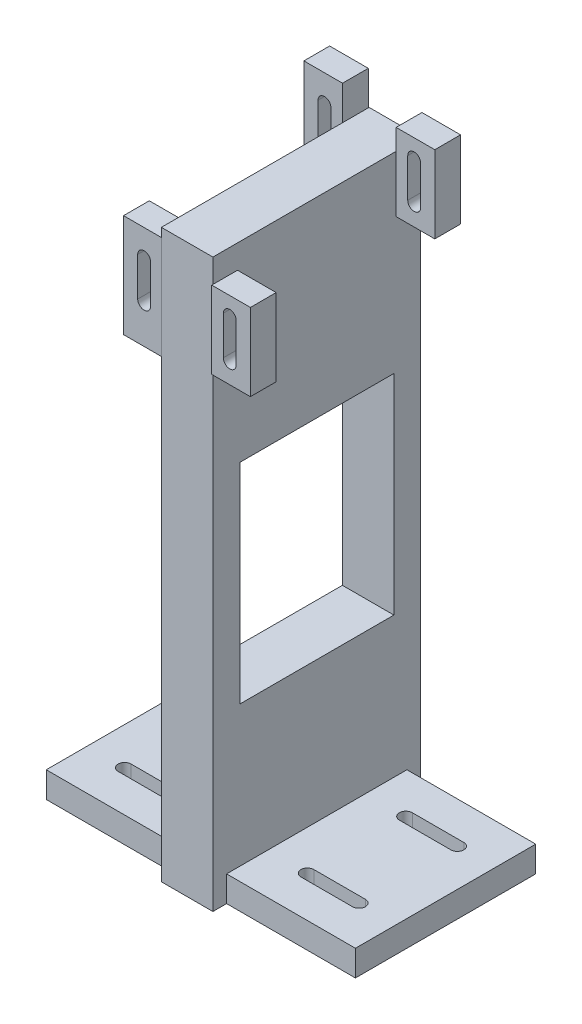
SolidWorks part; units mm, degrees
ref_plane "Płaszczyzna przednia" through (0, 0, 0) normal (0, 0, 1) x (1, 0, 0)
ref_plane "Płaszczyzna górna" through (0, 0, 0) normal (0, 1, 0) x (1, 0, 0)
ref_plane "Płaszczyzna prawa" through (0, 0, 0) normal (1, 0, 0) x (0, 0, -1)
sketch "Sketch1" plane through (0, 0, 0) normal (0, 1, 0) x (1, 0, 0)
  line L0 (-60, 0) -> (60, 0) construction
  line L1 (-60, 35) -> (60, 35)
  line L2 (-60, 35) -> (-60, -35)
  line L3 (-60, -35) -> (60, -35)
  line L4 (60, 35) -> (60, -35)
  line L5 (0, 35) -> (0, -35) construction
  line L6 (-10, 40.3147) -> (-10, -40.3147)
  line L7 (10, 40.3147) -> (10, -40.3147)
  line L8 (-45.4696, 19.1036) -> (-25.4696, 19.1036) construction
  line L9 (-45.4696, 21.6036) -> (-25.4696, 21.6036)
  line L10 (-45.4696, 16.6036) -> (-25.4696, 16.6036)
  line L11 (45.4696, 19.1036) -> (25.4696, 19.1036) construction
  line L13 (45.4696, 21.6036) -> (25.4696, 21.6036)
  line L14 (45.4696, 16.6036) -> (25.4696, 16.6036)
  line L15 (45.4696, -19.1036) -> (25.4696, -19.1036) construction
  line L16 (45.4696, -21.6036) -> (25.4696, -21.6036)
  line L17 (45.4696, -16.6036) -> (25.4696, -16.6036)
  line L18 (-45.4696, -19.1036) -> (-25.4696, -19.1036) construction
  line L19 (-45.4696, -21.6036) -> (-25.4696, -21.6036)
  line L20 (-45.4696, -16.6036) -> (-25.4696, -16.6036)
  line L21 (-10, 40.3147) -> (10, 40.3147)
  line L22 (10, -40.3147) -> (-10, -40.3147)
  arc A8 (-45.4696, 21.6036) -> (-45.4696, 16.6036) centre (-45.4696, 19.1036) ccw
  arc A9 (-25.4696, 16.6036) -> (-25.4696, 21.6036) centre (-25.4696, 19.1036) ccw
  arc A10 (45.4696, 21.6036) -> (45.4696, 16.6036) centre (45.4696, 19.1036) cw
  arc A11 (25.4696, 16.6036) -> (25.4696, 21.6036) centre (25.4696, 19.1036) cw
  arc A12 (45.4696, -21.6036) -> (45.4696, -16.6036) centre (45.4696, -19.1036) ccw
  arc A13 (25.4696, -16.6036) -> (25.4696, -21.6036) centre (25.4696, -19.1036) ccw
  arc A14 (-45.4696, -21.6036) -> (-45.4696, -16.6036) centre (-45.4696, -19.1036) cw
  arc A15 (-25.4696, -16.6036) -> (-25.4696, -21.6036) centre (-25.4696, -19.1036) cw
  point P17 (-35.4696, 19.1036)
  point P30 (35.4696, 19.1036)
  point P41 (35.4696, -19.1036)
  point P48 (-35.4696, -19.1036)
  dimension "D4" = 20
  dimension "D1" = 120
  dimension "D2" = 70
  dimension "D3" = 20
  dimension "D6" = 5
extrude "Boss-Extrude1" add sketch "Sketch1" along normal blind 10 contours A15 L20 A14 L19 | L10 A9 L9 A8 | A11 L14 A10 L13 | L17 A13 L16 A12 | L3 L4 L1 L2 region at (-35.4696, 0, -19.1036) region at (35.4696, 0, -19.1036) region at (35.4696, 0, 19.1036) region at (-35.4696, 0, 19.1036)
extrude "Boss-Extrude2" add sketch "Sketch1<3>" along normal blind 220 contours L7 L1 L6 L3 | L21 L6 L1 L7 | L22 L7 L3 L6 region at (0, 0, -37.6574) region at (0, 0, 0) region at (0, 0, 37.6574)
sketch "Sketch1<3>" plane through (0, 0, 0) normal (0, 1, 0) x (1, 0, 0) same geometry as "Sketch1"
sketch "Sketch2" plane through (10, 0, 0) normal (1, 0, 0) x (0, 0, -1)
  line L5 (-30, 216.2685) -> (-40, 216.2685)
  line L6 (-30, 216.2685) -> (-30, 176.2685)
  line L7 (-30, 176.2685) -> (-40, 176.2685)
  line L8 (-40, 216.2685) -> (-40, 176.2685)
  line L10 (30, 233.2933) -> (40, 233.2933)
  line L11 (30, 233.2933) -> (30, 158.5233)
  line L12 (30, 158.5233) -> (40, 158.5233)
  line L13 (40, 233.2933) -> (40, 158.5233)
  line L14 (0, 220) -> (0, 77.9938) construction
  line L15 (40.3147, 220) -> (-40.3147, 220) construction
  dimension "D1" = 60
  dimension "D2" = 10
  dimension "D3" = 40
extrude "Boss-Extrude3" add sketch "Sketch2" against normal blind 15 from surface starting at face at (-10, 57.5, 0)
sketch "Sketch3" plane through (10, 0, 0) normal (1, 0, 0) x (0, 0, -1)
  line L1 (-29.7814, 145.7552) -> (29.9449, 145.7552)
  line L2 (-29.7814, 145.7552) -> (-29.7814, 64.5274)
  line L3 (-29.7814, 64.5274) -> (29.9449, 64.5274)
  line L4 (29.9449, 145.7552) -> (29.9449, 64.5274)
extrude "Cut-Extrude1" cut sketch "Sketch3" against normal blind 60
sketch "Sketch4" plane through (0, 0, 40) normal (0, 0, 1) x (1, 0, 0)
  line L0 (-17, 205.9837) -> (-17, 190.9837) construction
  line L1 (-14.5, 205.9837) -> (-14.5, 190.9837)
  line L2 (-19.5, 205.9837) -> (-19.5, 190.9837)
  line L3 (-10, 220) -> (-10, 0) construction
  arc A0 (-14.5, 205.9837) -> (-19.5, 205.9837) centre (-17, 205.9837) ccw
  arc A1 (-19.5, 190.9837) -> (-14.5, 190.9837) centre (-17, 190.9837) ccw
  point P2 (-17, 198.4837)
  point P7 (-19.0815, 198.3469)
  point P10 (-17, 205.9837)
  point P11 (0, 0)
  dimension "D1" = 5
  dimension "D2" = 15
  dimension "D3" = 7
extrude "Cut-Extrude2" cut sketch "Sketch4" against normal up to next
sketch "Sketch5" plane through (0, 0, -40) normal (0, 0, -1) x (-1, 0, 0)
  line L0 (17, 222.8197) -> (17, 207.8197) construction
  line L1 (19.5, 222.8197) -> (19.5, 207.8197)
  line L2 (14.5, 222.8197) -> (14.5, 207.8197)
  line L3 (10, 220) -> (10, 233.2933) construction
  line L4 (17, 183.2065) -> (17, 168.2065) construction
  line L5 (19.5, 183.2065) -> (19.5, 168.2065)
  line L6 (14.5, 183.2065) -> (14.5, 168.2065)
  arc A0 (19.5, 222.8197) -> (14.5, 222.8197) centre (17, 222.8197) ccw
  arc A1 (14.5, 207.8197) -> (19.5, 207.8197) centre (17, 207.8197) ccw
  arc A2 (19.5, 183.2065) -> (14.5, 183.2065) centre (17, 183.2065) ccw
  arc A3 (14.5, 168.2065) -> (19.5, 168.2065) centre (17, 168.2065) ccw
  point P2 (17, 215.3197)
  point P11 (17, 175.7065)
  point P16 (17, 169.0011)
  point P17 (17, 174.696)
  point P18 (17, 176.3471)
  point P19 (17, 175.7065)
  point P20 (17, 215.3197)
  dimension "D1" = 15
  dimension "D2" = 5
  dimension "D3" = 7
extrude "Cut-Extrude3" cut sketch "Sketch5" against normal up to next
ref_plane "Plane1" through (0, 0, 0) normal (0, 0, 1) x (1, 0, 0)
sketch "Sketch6" plane through (10, 0, 0) normal (1, 0, 0) x (0, 0, -1)
  line L1 (-30.7639, 210.7964) -> (-40.7639, 210.7964)
  line L2 (-30.7639, 210.7964) -> (-30.7639, 180.7964)
  line L3 (-30.7639, 180.7964) -> (-40.7639, 180.7964)
  line L4 (-40.7639, 210.7964) -> (-40.7639, 180.7964)
  line L5 (30.8125, 228.0299) -> (40.8125, 228.0299)
  line L6 (30.8125, 228.0299) -> (30.8125, 198.0299)
  line L7 (30.8125, 198.0299) -> (40.8125, 198.0299)
  line L8 (40.8125, 228.0299) -> (40.8125, 198.0299)
  dimension "D1" = 10
  dimension "D2" = 30
extrude "Boss-Extrude4" add sketch "Sketch6" along normal blind 15
sketch "Sketch7" plane through (0, 0, 40.7639) normal (0, 0, 1) x (1, 0, 0)
  line L0 (17, 203.6241) -> (17, 188.6241) construction
  line L1 (19.5, 203.6241) -> (19.5, 188.6241)
  line L2 (14.5, 203.6241) -> (14.5, 188.6241)
  line L3 (10, 210.7964) -> (10, 180.7964) construction
  arc A0 (19.5, 203.6241) -> (14.5, 203.6241) centre (17, 203.6241) ccw
  arc A1 (14.5, 188.6241) -> (19.5, 188.6241) centre (17, 188.6241) ccw
  point P2 (17, 196.1241)
  point P9 (17, 196.1241)
  dimension "D1" = 15
  dimension "D2" = 5
  dimension "D3" = 7
extrude "Cut-Extrude4" cut sketch "Sketch7" against normal up to next
sketch "Sketch8" plane through (0, 0, -40.8125) normal (0, 0, -1) x (-1, 0, 0)
  line L0 (-17, 220.7806) -> (-17, 205.7806) construction
  line L1 (-14.5, 220.7806) -> (-14.5, 205.7806)
  line L2 (-19.5, 220.7806) -> (-19.5, 205.7806)
  line L3 (-10, 198.0299) -> (-10, 228.0299) construction
  arc A0 (-14.5, 220.7806) -> (-19.5, 220.7806) centre (-17, 220.7806) ccw
  arc A1 (-19.5, 205.7806) -> (-14.5, 205.7806) centre (-17, 205.7806) ccw
  point P2 (-17, 213.2806)
  dimension "D1" = 5
  dimension "D2" = 15
  dimension "D3" = 7
extrude "Cut-Extrude5" cut sketch "Sketch8" against normal up to next
